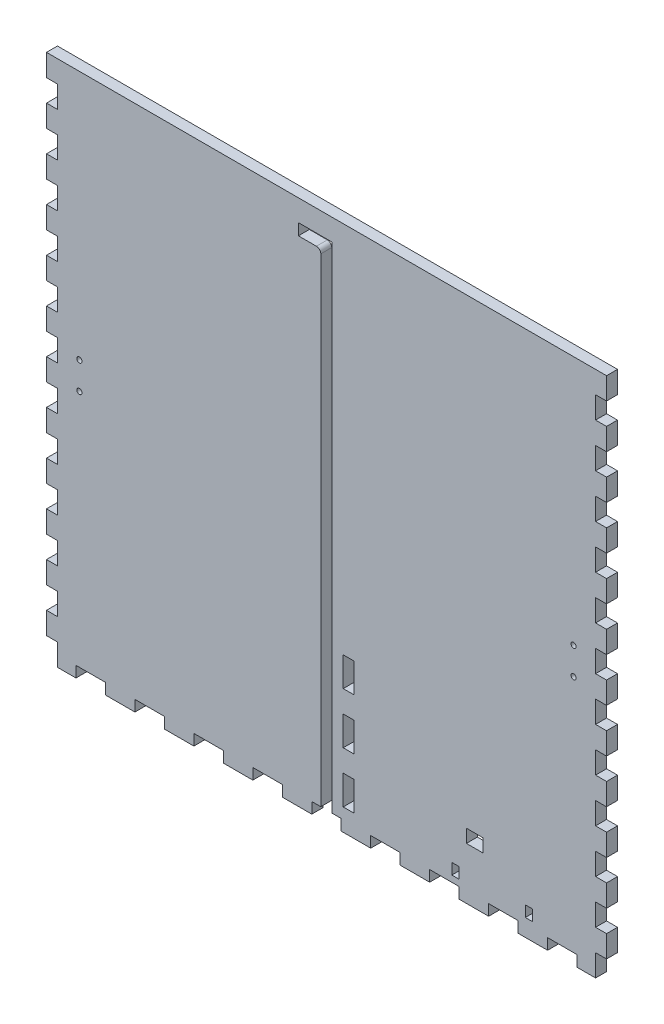
SolidWorks part; units mm, degrees
material "Acrylic (Medium-high impact)"
ref_plane "Front Plane" through (0, 0, 0) normal (0, 0, 1) x (1, 0, 0)
ref_plane "Top Plane" through (0, 0, 0) normal (0, 1, 0) x (1, 0, 0)
ref_plane "Right Plane" through (0, 0, 0) normal (1, 0, 0) x (0, 0, -1)
sketch "Sketch1" plane through (0, 0, 0) normal (0, 1, 0) x (1, 0, 0)
  line L1 (-161.925, 69.85) -> (161.925, 69.85)
  line L2 (-161.925, 69.85) -> (-161.925, -69.85)
  line L3 (-161.925, -69.85) -> (161.925, -69.85)
  line L4 (161.925, 69.85) -> (161.925, -69.85)
  point P4 (-161.925, 0)
  point P6 (0, 69.85)
  dimension "D1" = 139.7
  dimension "D2" = 323.85
extrude "Boss-Extrude1" add sketch "Sketch1" along normal blind 6.35
sketch "Sketch2" plane through (0, 6.35, 0) normal (0, 1, 0) x (1, 0, 0)
  line L0 (161.925, -69.85) -> (161.925, 69.85) construction
  line L1 (-161.925, 69.85) -> (161.925, 69.85)
  line L2 (-161.925, 69.85) -> (-161.925, -69.85)
  line L3 (-161.925, -69.85) -> (161.925, -69.85)
  line L4 (161.925, 69.85) -> (161.925, -69.85)
  line L5 (-161.925, -69.85) -> (161.925, -69.85) construction
  line L7 (-155.575, 63.5) -> (155.575, 63.5)
  line L8 (-155.575, 63.5) -> (-155.575, -63.5)
  line L9 (-155.575, -63.5) -> (155.575, -63.5)
  line L10 (155.575, 63.5) -> (155.575, -63.5)
  point P7 (-155.575, 0)
  point P14 (-161.925, 0)
  point P15 (0, -63.5)
  point P16 (0, -69.85)
  point P17 (155.575, 0)
  point P18 (161.925, 0)
  dimension "D1" = 6.35
  dimension "D2" = 6.35
extrude "Boss-Extrude2" add sketch "Sketch2" along normal blind 298.45
sketch "Sketch3" plane through (0, 0, 69.85) normal (0, 0, 1) x (1, 0, 0)
  line L0 (0, 304.8) -> (0, 0) construction
  line L2 (-155.575, 6.35) -> (155.575, 6.35) construction
  line L4 (-3.302, 283.21) -> (-3.302, 6.35)
  line L5 (-3.302, 6.35) -> (3.302, 6.35)
  line L6 (3.302, 292.354) -> (3.302, 6.35)
  line L7 (3.302, 292.354) -> (-16.256, 292.354)
  line L9 (-5.842, 285.75) -> (-16.256, 285.75)
  line L10 (-16.256, 292.354) -> (-16.256, 285.75)
  line L11 (3.302, 101.6) -> (16.002, 101.6) construction
  line L12 (-161.925, 0) -> (161.925, 0) construction
  line L13 (12.827, 88.9) -> (12.827, 101.6) construction
  line L14 (9.652, 88.9) -> (16.002, 88.9)
  line L15 (9.652, 88.9) -> (9.652, 71.9667)
  line L16 (9.652, 71.9667) -> (16.002, 71.9667)
  line L17 (16.002, 88.9) -> (16.002, 71.9667)
  line L18 (9.652, 42.3333) -> (16.002, 42.3333)
  line L19 (9.652, 42.3333) -> (9.652, 59.2667)
  line L20 (9.652, 59.2667) -> (16.002, 59.2667)
  line L21 (16.002, 42.3333) -> (16.002, 59.2667)
  line L26 (9.652, 29.6333) -> (16.002, 29.6333)
  line L27 (9.652, 29.6333) -> (9.652, 12.7)
  line L28 (9.652, 12.7) -> (16.002, 12.7)
  line L29 (16.002, 29.6333) -> (16.002, 12.7)
  line L30 (12.827, 59.2667) -> (12.827, 71.9667) construction
  line L31 (12.827, 29.6333) -> (12.827, 42.3333) construction
  line L32 (12.827, 12.7) -> (12.827, 0) construction
  line L33 (-161.925, 304.8) -> (161.925, 304.8) construction
  arc A0 (-3.302, 283.21) -> (-5.842, 285.75) centre (-5.842, 283.21) ccw
  point P5 (0, 6.35)
  point P44 (0, 0)
  dimension "D5" = 2.54
  dimension "D1" = 6.604
  dimension "D2" = 12.954
  dimension "D3" = 6.604
  dimension "D4" = 286.004
  dimension "D6" = 101.6
  dimension "D7" = 12.7
  dimension "D8" = 12.7
  dimension "D9" = 6.35
extrude "Door Slot" cut sketch "Sketch3" against normal blind 12.7
sketch "Sketch4" plane through (0, 0, -63.5) normal (0, 0, 1) x (1, 0, 0)
  line L0 (-161.925, 304.8) -> (161.925, 304.8) construction
  line L1 (-22.606, 304.8) -> (-16.256, 304.8)
  line L2 (-22.606, 304.8) -> (-22.606, 6.35)
  line L3 (-22.606, 6.35) -> (-16.256, 6.35)
  line L4 (-16.256, 304.8) -> (-16.256, 6.35)
  line L5 (6.477, 263.525) -> (6.477, 247.65) construction
  line L6 (-16.256, 292.354) -> (-16.256, 285.75) construction
  line L7 (3.302, 304.8) -> (9.652, 304.8)
  line L8 (3.302, 304.8) -> (3.302, 6.35)
  line L9 (3.302, 6.35) -> (9.652, 6.35)
  line L10 (9.652, 304.8) -> (9.652, 6.35)
  line L11 (155.575, 6.35) -> (-155.575, 6.35) construction
  line L12 (3.302, 6.35) -> (3.302, 292.354) construction
  line L13 (-16.256, 304.8) -> (-22.606, 304.8)
  line L14 (-16.256, 304.8) -> (-16.256, 292.1)
  line L15 (-16.256, 292.1) -> (-22.606, 292.1)
  line L16 (-22.606, 304.8) -> (-22.606, 292.1)
  line L17 (-16.256, 276.225) -> (-22.606, 276.225)
  line L18 (-16.256, 276.225) -> (-16.256, 263.525)
  line L19 (-16.256, 263.525) -> (-22.606, 263.525)
  line L20 (-22.606, 276.225) -> (-22.606, 263.525)
  line L21 (-22.606, 6.35) -> (-16.256, 6.35)
  line L22 (-22.606, 6.35) -> (-22.606, 19.05)
  line L23 (-22.606, 19.05) -> (-16.256, 19.05)
  line L24 (-16.256, 6.35) -> (-16.256, 19.05)
  line L25 (-22.606, 34.925) -> (-16.256, 34.925)
  line L26 (-22.606, 34.925) -> (-22.606, 47.625)
  line L27 (-22.606, 47.625) -> (-16.256, 47.625)
  line L28 (-16.256, 34.925) -> (-16.256, 47.625)
  line L29 (-22.606, 92.075) -> (-16.256, 92.075)
  line L30 (-22.606, 92.075) -> (-22.606, 104.775)
  line L31 (-22.606, 104.775) -> (-16.256, 104.775)
  line L32 (-16.256, 92.075) -> (-16.256, 104.775)
  line L33 (-22.606, 149.225) -> (-16.256, 149.225)
  line L34 (-22.606, 149.225) -> (-22.606, 161.925)
  line L35 (-22.606, 161.925) -> (-16.256, 161.925)
  line L36 (-16.256, 149.225) -> (-16.256, 161.925)
  line L37 (-22.606, 177.8) -> (-16.256, 177.8)
  line L38 (-22.606, 177.8) -> (-22.606, 190.5)
  line L39 (-22.606, 190.5) -> (-16.256, 190.5)
  line L40 (-16.256, 177.8) -> (-16.256, 190.5)
  line L41 (-22.606, 206.375) -> (-16.256, 206.375)
  line L42 (-22.606, 206.375) -> (-22.606, 219.075)
  line L43 (-22.606, 219.075) -> (-16.256, 219.075)
  line L44 (-16.256, 206.375) -> (-16.256, 219.075)
  line L45 (-22.606, 234.95) -> (-16.256, 234.95)
  line L46 (-22.606, 234.95) -> (-22.606, 247.65)
  line L47 (-22.606, 247.65) -> (-16.256, 247.65)
  line L48 (-16.256, 234.95) -> (-16.256, 247.65)
  line L49 (-16.256, 133.35) -> (-22.606, 133.35)
  line L50 (-16.256, 133.35) -> (-16.256, 120.65)
  line L51 (-16.256, 120.65) -> (-22.606, 120.65)
  line L52 (-22.606, 133.35) -> (-22.606, 120.65)
  line L53 (-16.256, 76.2) -> (-22.606, 76.2)
  line L54 (-16.256, 76.2) -> (-16.256, 63.5)
  line L55 (-16.256, 63.5) -> (-22.606, 63.5)
  line L56 (-22.606, 76.2) -> (-22.606, 63.5)
  line L57 (-19.431, 304.8) -> (-19.431, 292.1) construction
  line L58 (-19.431, 292.1) -> (-19.431, 276.225) construction
  line L59 (-19.431, 276.225) -> (-19.431, 263.525) construction
  line L60 (-19.431, 247.65) -> (-19.431, 234.95) construction
  line L61 (-19.431, 234.95) -> (-19.431, 219.075) construction
  line L62 (-19.431, 219.075) -> (-19.431, 206.375) construction
  line L63 (-19.431, 206.375) -> (-19.431, 190.5) construction
  line L64 (-19.431, 190.5) -> (-19.431, 177.8) construction
  line L65 (-19.431, 177.8) -> (-19.431, 161.925) construction
  line L66 (-19.431, 161.925) -> (-19.431, 149.225) construction
  line L67 (-19.431, 133.35) -> (-19.431, 120.65) construction
  line L68 (-19.431, 120.65) -> (-19.431, 104.775) construction
  line L69 (-19.431, 104.775) -> (-19.431, 92.075) construction
  line L70 (-19.431, 92.075) -> (-19.431, 76.2) construction
  line L71 (-19.431, 76.2) -> (-19.431, 63.5) construction
  line L72 (-19.431, 63.5) -> (-19.431, 47.625) construction
  line L73 (-19.431, 47.625) -> (-19.431, 34.925) construction
  line L74 (-19.431, 34.925) -> (-19.431, 19.05) construction
  line L75 (-19.431, 19.05) -> (-19.431, 6.35) construction
  line L76 (-19.431, 149.225) -> (-19.431, 133.35) construction
  line L77 (-19.431, 263.525) -> (-19.431, 247.65) construction
  line L78 (-6.477, 304.8) -> (-6.477, 0) construction
  line L79 (161.925, 304.8) -> (-161.925, 304.8) construction
  line L80 (161.925, 0) -> (-161.925, 0) construction
  line L81 (-6.477, 8.3493) -> (3.302, 8.3493) construction
  line L82 (-6.477, 8.3493) -> (-16.256, 8.3493) construction
  line L83 (6.477, 149.225) -> (6.477, 133.35) construction
  line L84 (6.477, 19.05) -> (6.477, 6.35) construction
  line L85 (6.477, 34.925) -> (6.477, 19.05) construction
  line L86 (6.477, 47.625) -> (6.477, 34.925) construction
  line L87 (6.477, 63.5) -> (6.477, 47.625) construction
  line L88 (6.477, 76.2) -> (6.477, 63.5) construction
  line L89 (6.477, 92.075) -> (6.477, 76.2) construction
  line L90 (6.477, 104.775) -> (6.477, 92.075) construction
  line L91 (6.477, 120.65) -> (6.477, 104.775) construction
  line L92 (6.477, 133.35) -> (6.477, 120.65) construction
  line L93 (6.477, 161.925) -> (6.477, 149.225) construction
  line L94 (6.477, 177.8) -> (6.477, 161.925) construction
  line L95 (6.477, 190.5) -> (6.477, 177.8) construction
  line L96 (6.477, 206.375) -> (6.477, 190.5) construction
  line L97 (6.477, 219.075) -> (6.477, 206.375) construction
  line L98 (6.477, 234.95) -> (6.477, 219.075) construction
  line L99 (6.477, 247.65) -> (6.477, 234.95) construction
  line L100 (6.477, 276.225) -> (6.477, 263.525) construction
  line L101 (6.477, 292.1) -> (6.477, 276.225) construction
  line L102 (6.477, 304.8) -> (6.477, 292.1) construction
  line L103 (9.652, 76.2) -> (9.652, 63.5)
  line L104 (3.302, 63.5) -> (9.652, 63.5)
  line L105 (3.302, 76.2) -> (3.302, 63.5)
  line L106 (3.302, 76.2) -> (9.652, 76.2)
  line L107 (9.652, 133.35) -> (9.652, 120.65)
  line L108 (3.302, 120.65) -> (9.652, 120.65)
  line L109 (3.302, 133.35) -> (3.302, 120.65)
  line L110 (3.302, 133.35) -> (9.652, 133.35)
  line L111 (3.302, 234.95) -> (3.302, 247.65)
  line L112 (9.652, 247.65) -> (3.302, 247.65)
  line L113 (9.652, 234.95) -> (9.652, 247.65)
  line L114 (9.652, 234.95) -> (3.302, 234.95)
  line L115 (3.302, 206.375) -> (3.302, 219.075)
  line L116 (9.652, 219.075) -> (3.302, 219.075)
  line L117 (9.652, 206.375) -> (9.652, 219.075)
  line L118 (9.652, 206.375) -> (3.302, 206.375)
  line L119 (3.302, 177.8) -> (3.302, 190.5)
  line L120 (9.652, 190.5) -> (3.302, 190.5)
  line L121 (9.652, 177.8) -> (9.652, 190.5)
  line L122 (9.652, 177.8) -> (3.302, 177.8)
  line L123 (3.302, 149.225) -> (3.302, 161.925)
  line L124 (9.652, 161.925) -> (3.302, 161.925)
  line L125 (9.652, 149.225) -> (9.652, 161.925)
  line L126 (9.652, 149.225) -> (3.302, 149.225)
  line L127 (3.302, 92.075) -> (3.302, 104.775)
  line L128 (9.652, 104.775) -> (3.302, 104.775)
  line L129 (9.652, 92.075) -> (9.652, 104.775)
  line L130 (9.652, 92.075) -> (3.302, 92.075)
  line L131 (3.302, 34.925) -> (3.302, 47.625)
  line L132 (9.652, 47.625) -> (3.302, 47.625)
  line L133 (9.652, 34.925) -> (9.652, 47.625)
  line L134 (9.652, 34.925) -> (3.302, 34.925)
  line L135 (3.302, 6.35) -> (3.302, 19.05)
  line L136 (9.652, 19.05) -> (3.302, 19.05)
  line L137 (9.652, 6.35) -> (9.652, 19.05)
  line L138 (9.652, 6.35) -> (3.302, 6.35)
  line L139 (9.652, 276.225) -> (9.652, 263.525)
  line L140 (3.302, 263.525) -> (9.652, 263.525)
  line L141 (3.302, 276.225) -> (3.302, 263.525)
  line L142 (3.302, 276.225) -> (9.652, 276.225)
  line L143 (9.652, 304.8) -> (9.652, 292.1)
  line L144 (3.302, 292.1) -> (9.652, 292.1)
  line L145 (3.302, 304.8) -> (3.302, 292.1)
  line L146 (3.302, 304.8) -> (9.652, 304.8)
  line L147 (3.302, 304.8) -> (3.302, 6.35)
  line L148 (9.652, 6.35) -> (3.302, 6.35)
  line L149 (9.652, 304.8) -> (9.652, 6.35)
  line L150 (9.652, 304.8) -> (3.302, 304.8)
  point P14 (-16.256, 289.052)
  dimension "D1" = 6.35
  dimension "D2" = 12.7
extrude "Door Guide Holes" cut sketch "Sketch4" against normal up to next contours L17 L4 L15 L2 | L2 L47 L4 L19 | L45 L2 L43 L4 | L41 L2 L39 L4 | L37 L2 L35 L4 | L49 L4 L33 L2 | L4 L51 L2 L31 | L53 L4 L29 L2 | L4 L55 L2 L27 | L25 L2 L23 L4 region at (-19.431, 284.1625, -63.5) region at (-19.431, 255.5875, -63.5) region at (-19.431, 227.0125, -63.5) region at (-19.431, 198.4375, -63.5) region at (-19.431, 169.8625, -63.5) region at (-19.431, 141.2875, -63.5) region at (-19.431, 112.7125, -63.5) region at (-19.431, 84.1375, -63.5) region at (-19.431, 55.5625, -63.5) region at (-19.431, 26.9875, -63.5)
ref_plane "Plane1" through (-6.477, 0, 0) normal (-1, 0, 0) x (0, 0, 1)
mirror "Mirror1" about plane through (-6.477, 0, 0) normal (-1, 0, 0) of "Door Guide Holes"
sketch "Lever Holes" plane through (0, 0, 69.85) normal (0, 0, 1) x (1, 0, 0)
  line L0 (80.899, 37.685) -> (90.551, 37.685)
  line L1 (80.899, 37.685) -> (80.899, 30.065)
  line L2 (80.899, 30.065) -> (90.551, 30.065)
  line L3 (90.551, 37.685) -> (90.551, 30.065)
  line L4 (72.475, 16.35) -> (76.475, 16.35)
  line L5 (72.475, 16.35) -> (72.475, 10)
  line L6 (72.475, 10) -> (76.475, 10)
  line L7 (76.475, 16.35) -> (76.475, 10)
  line L8 (114.975, 16.35) -> (118.975, 16.35)
  line L9 (114.975, 16.35) -> (114.975, 10)
  line L10 (114.975, 10) -> (118.975, 10)
  line L11 (118.975, 16.35) -> (118.975, 10)
  line L12 (76.475, 13.175) -> (114.975, 13.175) construction
  line L14 (3.302, 6.35) -> (155.575, 6.35) construction
  line L15 (155.575, 6.35) -> (-155.575, 6.35) construction
  line L16 (142.875, 160.275) -> (142.875, 144.525) construction
  line L17 (161.925, 304.8) -> (161.925, 0) construction
  line L18 (0, -76.835) -> (0, 76.835) construction
  circle A0 centre (142.875, 160.275) radius 1.5
  circle A1 centre (142.875, 144.525) radius 1.5
  circle A2 centre (-142.875, 160.275) radius 1.5
  circle A3 centre (-142.875, 144.525) radius 1.5
  point P13 (85.725, 30.065)
  point P31 (142.875, 152.4)
  point P32 (161.925, 152.4)
  dimension "D10" = 3
  dimension "D1" = 9.652
  dimension "D2" = 7.62
  dimension "D3" = 4
  dimension "D4" = 6.35
  dimension "D5" = 38.5
  dimension "D6" = 31.335
  dimension "D7" = 10
  dimension "D8" = 76.2
  dimension "D9" = 13.25
  dimension "D11" = 15.75
  dimension "D12" = 19.05
extrude "LeverHole Cut" cut sketch "Lever Holes" against normal through all
sketch "Sketch7" plane through (161.925, 0, 0) normal (1, 0, 0) x (0, 0, -1)
  line L0 (-37.211, 92.583) -> (37.211, 92.583)
  line L1 (-37.211, 92.583) -> (-37.211, 18.161)
  line L2 (-37.211, 18.161) -> (37.211, 18.161)
  line L3 (37.211, 92.583) -> (37.211, 18.161)
  line L4 (-69.85, 0) -> (69.85, 0) construction
  circle A0 centre (0, 55.372) radius 26.9875
  circle A1 centre (-37.211, 92.583) radius 3.175
  circle A2 centre (37.211, 92.583) radius 3.175
  circle A3 centre (-37.211, 18.161) radius 3.175
  circle A4 centre (37.211, 18.161) radius 3.175
  point P9 (0, 18.161)
  point P10 (-37.211, 55.372)
  dimension "D3" = 53.975
  dimension "D4" = 6.35
  dimension "D1" = 74.422
  dimension "D2" = 55.372
extrude "Cut-Extrude2" cut sketch "Sketch7" against normal up to next contours A0 | L0 A1 L1 | L1 A1 L0 | L3 A2 L0 | L0 A2 L3 | L2 A3 L1 | L1 A3 L2 | L2 A4 L3 | L3 A4 L2 region at (161.925, 93.0322, 37.6602) region at (161.925, 91.2355, 35.8635) region at (161.925, 93.0322, -37.6602) region at (161.925, 91.2355, -35.8635) region at (161.925, 19.5085, 35.8635) region at (161.925, 17.7118, 37.6602) region at (161.925, 17.7118, -37.6602) region at (161.925, 19.5085, -35.8635) region at (161.925, 55.372, 0)
sketch "Sketch8" plane through (-161.925, 0, 0) normal (-1, 0, 0) x (0, 0, 1)
  line L0 (-69.85, 0) -> (69.85, 0) construction
  circle A0 centre (0, 19.05) radius 3.175
  point P6 (0, 0)
  dimension "D1" = 6.35
  dimension "D2" = 19.05
extrude "Cut-Extrude3" cut sketch "Sketch8" against normal up to next
sketch "Bottom" plane through (0, 0, 0) normal (0, -1, 0) x (1, 0, 0)
  line L0 (-155.575, 63.5) -> (155.575, 63.5) construction
  line L1 (-161.925, 69.85) -> (-144.8803, 69.85)
  line L2 (-161.925, 69.85) -> (-161.925, 63.5)
  line L3 (-161.925, 63.5) -> (-144.8803, 63.5)
  line L4 (-144.8803, 69.85) -> (-144.8803, 63.5)
  line L5 (-144.8803, 69.85) -> (-127.8355, 69.85)
  line L6 (-144.8803, 69.85) -> (-144.8803, 63.5)
  line L7 (-144.8803, 63.5) -> (-127.8355, 63.5)
  line L8 (-127.8355, 69.85) -> (-127.8355, 63.5)
  line L9 (-127.8355, 69.85) -> (-110.7908, 69.85)
  line L10 (-127.8355, 69.85) -> (-127.8355, 63.5)
  line L11 (-127.8355, 63.5) -> (-110.7908, 63.5)
  line L12 (-110.7908, 69.85) -> (-110.7908, 63.5)
  line L13 (-110.7908, 69.85) -> (-93.7461, 69.85)
  line L14 (-110.7908, 69.85) -> (-110.7908, 63.5)
  line L15 (-110.7908, 63.5) -> (-93.7461, 63.5)
  line L16 (-93.7461, 69.85) -> (-93.7461, 63.5)
  line L17 (-161.925, 69.85) -> (161.925, 69.85) construction
  line L18 (-16.256, 63.5) -> (3.302, 63.5) construction
  line L19 (-93.7461, 69.85) -> (-76.7013, 69.85)
  line L20 (-93.7461, 69.85) -> (-93.7461, 63.5)
  line L21 (-93.7461, 63.5) -> (-76.7013, 63.5)
  line L22 (-76.7013, 69.85) -> (-76.7013, 63.5)
  line L23 (-76.7013, 69.85) -> (-59.6566, 69.85)
  line L24 (-76.7013, 69.85) -> (-76.7013, 63.5)
  line L25 (-76.7013, 63.5) -> (-59.6566, 63.5)
  line L26 (-59.6566, 69.85) -> (-59.6566, 63.5)
  line L27 (-59.6566, 69.85) -> (-42.6118, 69.85)
  line L28 (-59.6566, 69.85) -> (-59.6566, 63.5)
  line L29 (-59.6566, 63.5) -> (-42.6118, 63.5)
  line L30 (-42.6118, 69.85) -> (-42.6118, 63.5)
  line L31 (-42.6118, 69.85) -> (-25.5671, 69.85)
  line L32 (-42.6118, 69.85) -> (-42.6118, 63.5)
  line L33 (-42.6118, 63.5) -> (-25.5671, 63.5)
  line L34 (-25.5671, 69.85) -> (-25.5671, 63.5)
  line L36 (-25.5671, 69.85) -> (-8.5224, 69.85)
  line L37 (-25.5671, 69.85) -> (-25.5671, 63.5)
  line L38 (-25.5671, 63.5) -> (-8.5224, 63.5)
  line L39 (-8.5224, 69.85) -> (-8.5224, 63.5)
  line L40 (-8.5224, 69.85) -> (8.5224, 69.85)
  line L41 (-8.5224, 69.85) -> (-8.5224, 63.5)
  line L42 (-8.5224, 63.5) -> (8.5224, 63.5)
  line L43 (8.5224, 69.85) -> (8.5224, 63.5)
  line L44 (8.5224, 69.85) -> (25.5671, 69.85)
  line L45 (8.5224, 69.85) -> (8.5224, 63.5)
  line L46 (8.5224, 63.5) -> (25.5671, 63.5)
  line L47 (25.5671, 69.85) -> (25.5671, 63.5)
  line L48 (25.5671, 69.85) -> (42.6118, 69.85)
  line L49 (25.5671, 69.85) -> (25.5671, 63.5)
  line L50 (25.5671, 63.5) -> (42.6118, 63.5)
  line L51 (42.6118, 69.85) -> (42.6118, 63.5)
  line L52 (42.6118, 69.85) -> (59.6566, 69.85)
  line L53 (42.6118, 69.85) -> (42.6118, 63.5)
  line L54 (42.6118, 63.5) -> (59.6566, 63.5)
  line L55 (59.6566, 69.85) -> (59.6566, 63.5)
  line L56 (59.6566, 69.85) -> (76.7013, 69.85)
  line L57 (59.6566, 69.85) -> (59.6566, 63.5)
  line L58 (59.6566, 63.5) -> (76.7013, 63.5)
  line L59 (76.7013, 69.85) -> (76.7013, 63.5)
  line L60 (76.7013, 69.85) -> (93.7461, 69.85)
  line L61 (76.7013, 69.85) -> (76.7013, 63.5)
  line L62 (76.7013, 63.5) -> (93.7461, 63.5)
  line L63 (93.7461, 69.85) -> (93.7461, 63.5)
  line L64 (93.7461, 69.85) -> (110.7908, 69.85)
  line L65 (93.7461, 69.85) -> (93.7461, 63.5)
  line L66 (93.7461, 63.5) -> (110.7908, 63.5)
  line L67 (110.7908, 69.85) -> (110.7908, 63.5)
  line L68 (110.7908, 69.85) -> (127.8355, 69.85)
  line L69 (110.7908, 69.85) -> (110.7908, 63.5)
  line L70 (110.7908, 63.5) -> (127.8355, 63.5)
  line L71 (127.8355, 69.85) -> (127.8355, 63.5)
  line L72 (127.8355, 69.85) -> (144.8803, 69.85)
  line L73 (127.8355, 69.85) -> (127.8355, 63.5)
  line L74 (127.8355, 63.5) -> (144.8803, 63.5)
  line L75 (144.8803, 69.85) -> (144.8803, 63.5)
  line L76 (-155.575, -63.5) -> (-155.575, 63.5) construction
  line L77 (-161.925, 69.85) -> (-155.575, 69.85)
  line L78 (-161.925, 69.85) -> (-161.925, 57.15)
  line L79 (-161.925, 57.15) -> (-155.575, 57.15)
  line L80 (-155.575, 69.85) -> (-155.575, 57.15)
  line L82 (-161.925, 57.15) -> (-155.575, 57.15)
  line L83 (-161.925, 57.15) -> (-161.925, 44.45)
  line L84 (-161.925, 44.45) -> (-155.575, 44.45)
  line L85 (-155.575, 57.15) -> (-155.575, 44.45)
  line L86 (-161.925, 44.45) -> (-155.575, 44.45)
  line L87 (-161.925, 44.45) -> (-161.925, 31.75)
  line L88 (-161.925, 31.75) -> (-155.575, 31.75)
  line L89 (-155.575, 44.45) -> (-155.575, 31.75)
  line L90 (-161.925, 31.75) -> (-155.575, 31.75)
  line L91 (-161.925, 31.75) -> (-161.925, 19.05)
  line L92 (-161.925, 19.05) -> (-155.575, 19.05)
  line L93 (-155.575, 31.75) -> (-155.575, 19.05)
  line L94 (-161.925, 19.05) -> (-155.575, 19.05)
  line L95 (-161.925, 19.05) -> (-161.925, 6.35)
  line L96 (-161.925, 6.35) -> (-155.575, 6.35)
  line L97 (-155.575, 19.05) -> (-155.575, 6.35)
  line L98 (-161.925, 6.35) -> (-155.575, 6.35)
  line L99 (-161.925, 6.35) -> (-161.925, -6.35)
  line L100 (-161.925, -6.35) -> (-155.575, -6.35)
  line L101 (-155.575, 6.35) -> (-155.575, -6.35)
  line L102 (-161.925, -6.35) -> (-155.575, -6.35)
  line L103 (-161.925, -6.35) -> (-161.925, -19.05)
  line L104 (-161.925, -19.05) -> (-155.575, -19.05)
  line L105 (-155.575, -6.35) -> (-155.575, -19.05)
  line L106 (-161.925, -19.05) -> (-155.575, -19.05)
  line L107 (-161.925, -19.05) -> (-161.925, -31.75)
  line L108 (-161.925, -31.75) -> (-155.575, -31.75)
  line L109 (-155.575, -19.05) -> (-155.575, -31.75)
  line L110 (-161.925, -31.75) -> (-155.575, -31.75)
  line L111 (-161.925, -31.75) -> (-161.925, -44.45)
  line L112 (-161.925, -44.45) -> (-155.575, -44.45)
  line L113 (-155.575, -31.75) -> (-155.575, -44.45)
  line L114 (-161.925, -44.45) -> (-155.575, -44.45)
  line L115 (-161.925, -44.45) -> (-161.925, -57.15)
  line L116 (-161.925, -57.15) -> (-155.575, -57.15)
  line L117 (-155.575, -44.45) -> (-155.575, -57.15)
  line L118 (161.925, 69.85) -> (161.925, -69.85) construction
  line L119 (144.8803, 69.85) -> (161.925, 69.85)
  line L120 (144.8803, 69.85) -> (144.8803, 63.5)
  line L121 (144.8803, 63.5) -> (161.925, 63.5)
  line L122 (161.925, 69.85) -> (161.925, 63.5)
  line L123 (161.925, -69.85) -> (-161.925, -69.85) construction
  line L124 (-161.925, -57.15) -> (-155.575, -57.15)
  line L125 (-161.925, -57.15) -> (-161.925, -69.85)
  line L126 (-161.925, -69.85) -> (-155.575, -69.85)
  line L127 (-155.575, -57.15) -> (-155.575, -69.85)
  line L128 (167.64, 0) -> (-167.64, 0) construction
  line L129 (161.925, -69.85) -> (161.925, -63.5)
  line L130 (144.8803, -63.5) -> (161.925, -63.5)
  line L131 (144.8803, -69.85) -> (161.925, -69.85)
  line L132 (144.8803, -69.85) -> (144.8803, -63.5)
  line L133 (127.8355, -63.5) -> (144.8803, -63.5)
  line L134 (127.8355, -69.85) -> (144.8803, -69.85)
  line L135 (127.8355, -69.85) -> (127.8355, -63.5)
  line L136 (110.7908, -63.5) -> (127.8355, -63.5)
  line L137 (110.7908, -69.85) -> (127.8355, -69.85)
  line L138 (110.7908, -69.85) -> (110.7908, -63.5)
  line L139 (93.7461, -63.5) -> (110.7908, -63.5)
  line L140 (93.7461, -69.85) -> (110.7908, -69.85)
  line L141 (93.7461, -69.85) -> (93.7461, -63.5)
  line L142 (76.7013, -63.5) -> (93.7461, -63.5)
  line L143 (76.7013, -69.85) -> (93.7461, -69.85)
  line L144 (59.6566, -63.5) -> (76.7013, -63.5)
  line L145 (76.7013, -69.85) -> (76.7013, -63.5)
  line L146 (59.6566, -69.85) -> (76.7013, -69.85)
  line L147 (59.6566, -69.85) -> (59.6566, -63.5)
  line L148 (42.6118, -63.5) -> (59.6566, -63.5)
  line L149 (42.6118, -69.85) -> (59.6566, -69.85)
  line L150 (42.6118, -69.85) -> (42.6118, -63.5)
  line L151 (25.5671, -63.5) -> (42.6118, -63.5)
  line L152 (25.5671, -69.85) -> (42.6118, -69.85)
  line L153 (25.5671, -69.85) -> (25.5671, -63.5)
  line L154 (8.5224, -69.85) -> (25.5671, -69.85)
  line L155 (8.5224, -63.5) -> (25.5671, -63.5)
  line L156 (8.5224, -69.85) -> (8.5224, -63.5)
  line L157 (-8.5224, -63.5) -> (8.5224, -63.5)
  line L158 (-8.5224, -69.85) -> (8.5224, -69.85)
  line L159 (-25.5671, -63.5) -> (-8.5224, -63.5)
  line L160 (-8.5224, -69.85) -> (-8.5224, -63.5)
  line L161 (-25.5671, -69.85) -> (-8.5224, -69.85)
  line L162 (-25.5671, -69.85) -> (-25.5671, -63.5)
  line L163 (-42.6118, -63.5) -> (-25.5671, -63.5)
  line L164 (-42.6118, -69.85) -> (-25.5671, -69.85)
  line L165 (-42.6118, -69.85) -> (-42.6118, -63.5)
  line L166 (-59.6566, -63.5) -> (-42.6118, -63.5)
  line L167 (-59.6566, -69.85) -> (-42.6118, -69.85)
  line L168 (-59.6566, -69.85) -> (-59.6566, -63.5)
  line L169 (-76.7013, -69.85) -> (-59.6566, -69.85)
  line L170 (-76.7013, -63.5) -> (-59.6566, -63.5)
  line L171 (-93.7461, -63.5) -> (-76.7013, -63.5)
  line L172 (-76.7013, -69.85) -> (-76.7013, -63.5)
  line L173 (-93.7461, -69.85) -> (-76.7013, -69.85)
  line L174 (-110.7908, -69.85) -> (-93.7461, -69.85)
  line L175 (-110.7908, -63.5) -> (-93.7461, -63.5)
  line L176 (-93.7461, -69.85) -> (-93.7461, -63.5)
  line L177 (-127.8355, -69.85) -> (-127.8355, -63.5)
  line L178 (-127.8355, -69.85) -> (-110.7908, -69.85)
  line L179 (-110.7908, -69.85) -> (-110.7908, -63.5)
  line L180 (-127.8355, -63.5) -> (-110.7908, -63.5)
  line L181 (-144.8803, -63.5) -> (-127.8355, -63.5)
  line L182 (-144.8803, -69.85) -> (-127.8355, -69.85)
  line L183 (-144.8803, -69.85) -> (-144.8803, -63.5)
  line L184 (-161.925, -69.85) -> (-144.8803, -69.85)
  line L185 (-161.925, -69.85) -> (-161.925, -63.5)
  line L186 (-161.925, -63.5) -> (-144.8803, -63.5)
  line L187 (0, -76.835) -> (0, 76.835) construction
  line L188 (161.925, -69.85) -> (155.575, -69.85)
  line L189 (155.575, -57.15) -> (155.575, -69.85)
  line L190 (161.925, -57.15) -> (161.925, -69.85)
  line L191 (161.925, -57.15) -> (155.575, -57.15)
  line L192 (155.575, -44.45) -> (155.575, -57.15)
  line L193 (161.925, -44.45) -> (161.925, -57.15)
  line L194 (161.925, -44.45) -> (155.575, -44.45)
  line L195 (155.575, -31.75) -> (155.575, -44.45)
  line L196 (161.925, -31.75) -> (161.925, -44.45)
  line L197 (161.925, -31.75) -> (155.575, -31.75)
  line L198 (161.925, -19.05) -> (161.925, -31.75)
  line L199 (155.575, -19.05) -> (155.575, -31.75)
  line L200 (155.575, -6.35) -> (155.575, -19.05)
  line L201 (161.925, -6.35) -> (161.925, -19.05)
  line L202 (161.925, -19.05) -> (155.575, -19.05)
  line L203 (161.925, -6.35) -> (155.575, -6.35)
  line L204 (155.575, 6.35) -> (155.575, -6.35)
  line L205 (161.925, 6.35) -> (161.925, -6.35)
  line L206 (161.925, 6.35) -> (155.575, 6.35)
  line L207 (155.575, 19.05) -> (155.575, 6.35)
  line L208 (161.925, 19.05) -> (161.925, 6.35)
  line L209 (161.925, 19.05) -> (155.575, 19.05)
  line L210 (161.925, 31.75) -> (155.575, 31.75)
  line L211 (161.925, 44.45) -> (155.575, 44.45)
  line L212 (161.925, 57.15) -> (155.575, 57.15)
  line L213 (155.575, 31.75) -> (155.575, 19.05)
  line L214 (161.925, 31.75) -> (161.925, 19.05)
  line L215 (155.575, 44.45) -> (155.575, 31.75)
  line L216 (161.925, 44.45) -> (161.925, 31.75)
  line L217 (155.575, 57.15) -> (155.575, 44.45)
  line L218 (161.925, 57.15) -> (161.925, 44.45)
  line L219 (155.575, 69.85) -> (155.575, 57.15)
  line L220 (161.925, 69.85) -> (161.925, 57.15)
sketch "Front/Back" plane through (0, 0, 69.85) normal (0, 0, 1) x (1, 0, 0)
  line L0 (-155.575, 6.35) -> (-3.302, 6.35) construction
  line L1 (-161.925, 0) -> (-144.8803, 0)
  line L2 (-161.925, 0) -> (-161.925, 6.35)
  line L3 (-161.925, 6.35) -> (-144.8803, 6.35)
  line L4 (-144.8803, 0) -> (-144.8803, 6.35)
  line L5 (-161.925, 0) -> (161.925, 0) construction
  line L6 (-127.8355, 0) -> (-110.7908, 0) construction
  line L7 (-144.8803, 6.35) -> (-127.8355, 6.35)
  line L8 (-144.8803, 6.35) -> (-144.8803, 0)
  line L9 (-144.8803, 0) -> (-127.8355, 0)
  line L10 (-127.8355, 6.35) -> (-127.8355, 0)
  line L11 (-93.7461, 0) -> (-76.7013, 0) construction
  line L12 (-127.8355, 6.35) -> (-110.7908, 6.35)
  line L13 (-127.8355, 6.35) -> (-127.8355, 0)
  line L14 (-127.8355, 0) -> (-110.7908, 0)
  line L15 (-110.7908, 6.35) -> (-110.7908, 0)
  line L16 (-110.7908, 6.35) -> (-93.7461, 6.35)
  line L17 (-110.7908, 6.35) -> (-110.7908, 0)
  line L18 (-110.7908, 0) -> (-93.7461, 0)
  line L19 (-93.7461, 6.35) -> (-93.7461, 0)
  line L20 (-76.7013, 0) -> (-59.6566, 0) construction
  line L21 (-93.7461, 6.35) -> (-76.7013, 6.35)
  line L22 (-93.7461, 6.35) -> (-93.7461, 0)
  line L23 (-93.7461, 0) -> (-76.7013, 0)
  line L24 (-76.7013, 6.35) -> (-76.7013, 0)
  line L25 (-76.7013, 6.35) -> (-59.6566, 6.35)
  line L26 (-76.7013, 6.35) -> (-76.7013, 0)
  line L27 (-76.7013, 0) -> (-59.6566, 0)
  line L28 (-59.6566, 6.35) -> (-59.6566, 0)
  line L29 (-59.6566, 0) -> (-42.6118, 0) construction
  line L30 (-59.6566, 6.35) -> (-42.6118, 6.35)
  line L31 (-59.6566, 6.35) -> (-59.6566, 0)
  line L32 (-59.6566, 0) -> (-42.6118, 0)
  line L33 (-42.6118, 6.35) -> (-42.6118, 0)
  line L34 (-25.5671, 0) -> (-8.5224, 0) construction
  line L35 (-42.6118, 6.35) -> (-25.5671, 6.35)
  line L36 (-42.6118, 6.35) -> (-42.6118, 0)
  line L37 (-42.6118, 0) -> (-25.5671, 0)
  line L38 (-25.5671, 6.35) -> (-25.5671, 0)
  line L39 (8.5224, 0) -> (25.5671, 0) construction
  line L40 (-25.5671, 6.35) -> (-8.5224, 6.35)
  line L41 (-25.5671, 6.35) -> (-25.5671, 0)
  line L42 (-25.5671, 0) -> (-8.5224, 0)
  line L43 (-8.5224, 6.35) -> (-8.5224, 0)
  line L44 (-8.5224, 6.35) -> (8.5224, 6.35)
  line L45 (-8.5224, 6.35) -> (-8.5224, 0)
  line L46 (-8.5224, 0) -> (8.5224, 0)
  line L47 (8.5224, 6.35) -> (8.5224, 0)
  line L48 (8.5224, 0) -> (25.5671, 0) construction
  line L49 (42.6118, 0) -> (59.6566, 0) construction
  line L50 (8.5224, 6.35) -> (25.5671, 6.35)
  line L51 (8.5224, 6.35) -> (8.5224, 0)
  line L52 (8.5224, 0) -> (25.5671, 0)
  line L53 (25.5671, 6.35) -> (25.5671, 0)
  line L54 (25.5671, 6.35) -> (42.6118, 6.35)
  line L55 (25.5671, 6.35) -> (25.5671, 0)
  line L56 (25.5671, 0) -> (42.6118, 0)
  line L57 (42.6118, 6.35) -> (42.6118, 0)
  line L58 (76.7013, 0) -> (93.7461, 0) construction
  line L59 (42.6118, 6.35) -> (59.6566, 6.35)
  line L60 (42.6118, 6.35) -> (42.6118, 0)
  line L61 (42.6118, 0) -> (59.6566, 0)
  line L62 (59.6566, 6.35) -> (59.6566, 0)
  line L63 (59.6566, 6.35) -> (76.7013, 6.35)
  line L64 (59.6566, 6.35) -> (59.6566, 0)
  line L65 (59.6566, 0) -> (76.7013, 0)
  line L66 (76.7013, 6.35) -> (76.7013, 0)
  line L67 (59.6566, 0) -> (76.7013, 0) construction
  line L68 (110.7908, 0) -> (127.8355, 0) construction
  line L69 (76.7013, 6.35) -> (93.7461, 6.35)
  line L70 (76.7013, 6.35) -> (76.7013, 0)
  line L71 (76.7013, 0) -> (93.7461, 0)
  line L72 (93.7461, 6.35) -> (93.7461, 0)
  line L73 (93.7461, 6.35) -> (110.7908, 6.35)
  line L74 (93.7461, 6.35) -> (93.7461, 0)
  line L75 (93.7461, 0) -> (110.7908, 0)
  line L76 (110.7908, 6.35) -> (110.7908, 0)
  line L77 (127.8355, 0) -> (144.8803, 0) construction
  line L78 (110.7908, 6.35) -> (127.8355, 6.35)
  line L79 (110.7908, 6.35) -> (110.7908, 0)
  line L80 (110.7908, 0) -> (127.8355, 0)
  line L81 (127.8355, 6.35) -> (127.8355, 0)
  line L82 (127.8355, 0) -> (144.8803, 0) construction
  line L84 (127.8355, 6.35) -> (144.8803, 6.35)
  line L85 (127.8355, 6.35) -> (127.8355, 0)
  line L86 (127.8355, 0) -> (144.8803, 0)
  line L87 (144.8803, 6.35) -> (144.8803, 0)
  line L88 (144.8803, 6.35) -> (161.925, 6.35)
  line L89 (144.8803, 6.35) -> (144.8803, 0)
  line L90 (144.8803, 0) -> (161.925, 0)
  line L91 (161.925, 6.35) -> (161.925, 0)
  line L92 (-155.575, 304.8) -> (-155.575, 6.35) construction
  line L93 (-161.925, 0) -> (-155.575, 0)
  line L94 (-161.925, 0) -> (-161.925, 12.7)
  line L95 (-161.925, 12.7) -> (-155.575, 12.7)
  line L96 (-155.575, 0) -> (-155.575, 12.7)
  line L97 (-161.925, 304.8) -> (-161.925, 0) construction
  line L98 (-161.925, 12.7) -> (-155.575, 12.7)
  line L99 (-161.925, 12.7) -> (-161.925, 25.4)
  line L100 (-161.925, 25.4) -> (-155.575, 25.4)
  line L101 (-155.575, 12.7) -> (-155.575, 25.4)
  line L102 (-161.925, 25.4) -> (-155.575, 25.4)
  line L103 (-161.925, 25.4) -> (-161.925, 38.1)
  line L104 (-161.925, 38.1) -> (-155.575, 38.1)
  line L105 (-155.575, 25.4) -> (-155.575, 38.1)
  line L106 (-161.925, 38.1) -> (-155.575, 38.1)
  line L107 (-161.925, 38.1) -> (-161.925, 50.8)
  line L108 (-161.925, 50.8) -> (-155.575, 50.8)
  line L109 (-155.575, 38.1) -> (-155.575, 50.8)
  line L110 (-161.925, 50.8) -> (-155.575, 50.8)
  line L111 (-161.925, 50.8) -> (-161.925, 63.5)
  line L112 (-161.925, 63.5) -> (-155.575, 63.5)
  line L113 (-155.575, 50.8) -> (-155.575, 63.5)
  line L114 (-161.925, 63.5) -> (-155.575, 63.5)
  line L115 (-161.925, 63.5) -> (-161.925, 76.2)
  line L116 (-161.925, 76.2) -> (-155.575, 76.2)
  line L117 (-155.575, 63.5) -> (-155.575, 76.2)
  line L118 (-161.925, 76.2) -> (-155.575, 76.2)
  line L119 (-161.925, 76.2) -> (-161.925, 88.9)
  line L120 (-161.925, 88.9) -> (-155.575, 88.9)
  line L121 (-155.575, 76.2) -> (-155.575, 88.9)
  line L122 (-161.925, 88.9) -> (-155.575, 88.9)
  line L123 (-161.925, 88.9) -> (-161.925, 101.6)
  line L124 (-161.925, 101.6) -> (-155.575, 101.6)
  line L125 (-155.575, 88.9) -> (-155.575, 101.6)
  line L126 (-161.925, 101.6) -> (-155.575, 101.6)
  line L127 (-161.925, 101.6) -> (-161.925, 114.3)
  line L128 (-161.925, 114.3) -> (-155.575, 114.3)
  line L129 (-155.575, 101.6) -> (-155.575, 114.3)
  line L130 (-161.925, 114.3) -> (-155.575, 114.3)
  line L131 (-161.925, 114.3) -> (-161.925, 127)
  line L132 (-161.925, 127) -> (-155.575, 127)
  line L133 (-155.575, 114.3) -> (-155.575, 127)
  line L134 (-161.925, 127) -> (-155.575, 127)
  line L135 (-161.925, 127) -> (-161.925, 139.7)
  line L136 (-161.925, 139.7) -> (-155.575, 139.7)
  line L137 (-155.575, 127) -> (-155.575, 139.7)
  line L138 (-161.925, 139.7) -> (-155.575, 139.7)
  line L139 (-161.925, 139.7) -> (-161.925, 152.4)
  line L140 (-161.925, 152.4) -> (-155.575, 152.4)
  line L141 (-155.575, 139.7) -> (-155.575, 152.4)
  line L142 (-161.925, 152.4) -> (-155.575, 152.4)
  line L143 (-161.925, 152.4) -> (-161.925, 165.1)
  line L144 (-161.925, 165.1) -> (-155.575, 165.1)
  line L145 (-155.575, 152.4) -> (-155.575, 165.1)
  line L146 (-161.925, 165.1) -> (-155.575, 165.1)
  line L147 (-161.925, 165.1) -> (-161.925, 177.8)
  line L148 (-161.925, 177.8) -> (-155.575, 177.8)
  line L149 (-155.575, 165.1) -> (-155.575, 177.8)
  line L150 (-161.925, 177.8) -> (-155.575, 177.8)
  line L151 (-161.925, 177.8) -> (-161.925, 190.5)
  line L152 (-161.925, 190.5) -> (-155.575, 190.5)
  line L153 (-155.575, 177.8) -> (-155.575, 190.5)
  line L154 (-161.925, 190.5) -> (-155.575, 190.5)
  line L155 (-161.925, 190.5) -> (-161.925, 203.2)
  line L156 (-161.925, 203.2) -> (-155.575, 203.2)
  line L157 (-155.575, 190.5) -> (-155.575, 203.2)
  line L158 (-161.925, 203.2) -> (-155.575, 203.2)
  line L159 (-161.925, 203.2) -> (-161.925, 215.9)
  line L160 (-161.925, 215.9) -> (-155.575, 215.9)
  line L161 (-155.575, 203.2) -> (-155.575, 215.9)
  line L162 (-161.925, 215.9) -> (-155.575, 215.9)
  line L163 (-161.925, 215.9) -> (-161.925, 228.6)
  line L164 (-161.925, 228.6) -> (-155.575, 228.6)
  line L165 (-155.575, 215.9) -> (-155.575, 228.6)
  line L166 (-161.925, 228.6) -> (-155.575, 228.6)
  line L167 (-161.925, 228.6) -> (-161.925, 241.3)
  line L168 (-161.925, 241.3) -> (-155.575, 241.3)
  line L169 (-155.575, 228.6) -> (-155.575, 241.3)
  line L170 (-161.925, 241.3) -> (-155.575, 241.3)
  line L171 (-161.925, 241.3) -> (-161.925, 254)
  line L172 (-161.925, 254) -> (-155.575, 254)
  line L173 (-155.575, 241.3) -> (-155.575, 254)
  line L174 (-161.925, 254) -> (-155.575, 254)
  line L175 (-161.925, 254) -> (-161.925, 266.7)
  line L176 (-161.925, 266.7) -> (-155.575, 266.7)
  line L177 (-155.575, 254) -> (-155.575, 266.7)
  line L178 (-161.925, 266.7) -> (-155.575, 266.7)
  line L179 (-161.925, 266.7) -> (-161.925, 279.4)
  line L180 (-161.925, 279.4) -> (-155.575, 279.4)
  line L181 (-155.575, 266.7) -> (-155.575, 279.4)
  line L182 (-161.925, 279.4) -> (-155.575, 279.4)
  line L183 (-161.925, 279.4) -> (-161.925, 292.1)
  line L184 (-161.925, 292.1) -> (-155.575, 292.1)
  line L185 (-155.575, 279.4) -> (-155.575, 292.1)
  line L186 (-161.925, 292.1) -> (-155.575, 292.1)
  line L187 (-161.925, 292.1) -> (-161.925, 304.8)
  line L188 (-161.925, 304.8) -> (-155.575, 304.8)
  line L189 (-155.575, 292.1) -> (-155.575, 304.8)
  line L190 (-161.925, 304.8) -> (-155.575, 304.8)
  line L194 (-161.925, 304.8) -> (161.925, 304.8) construction
  line L195 (0, -76.835) -> (0, 76.835) construction
  line L196 (161.925, 304.8) -> (155.575, 304.8)
  line L197 (155.575, 292.1) -> (155.575, 304.8)
  line L198 (161.925, 304.8) -> (155.575, 304.8)
  line L199 (161.925, 292.1) -> (161.925, 304.8)
  line L200 (161.925, 292.1) -> (155.575, 292.1)
  line L201 (155.575, 279.4) -> (155.575, 292.1)
  line L202 (161.925, 292.1) -> (155.575, 292.1)
  line L203 (161.925, 279.4) -> (161.925, 292.1)
  line L204 (161.925, 279.4) -> (155.575, 279.4)
  line L205 (155.575, 266.7) -> (155.575, 279.4)
  line L206 (161.925, 279.4) -> (155.575, 279.4)
  line L207 (161.925, 266.7) -> (161.925, 279.4)
  line L208 (161.925, 266.7) -> (155.575, 266.7)
  line L209 (155.575, 254) -> (155.575, 266.7)
  line L210 (161.925, 266.7) -> (155.575, 266.7)
  line L211 (161.925, 254) -> (161.925, 266.7)
  line L212 (161.925, 254) -> (155.575, 254)
  line L213 (155.575, 241.3) -> (155.575, 254)
  line L214 (161.925, 254) -> (155.575, 254)
  line L215 (161.925, 241.3) -> (161.925, 254)
  line L216 (161.925, 241.3) -> (155.575, 241.3)
  line L217 (155.575, 228.6) -> (155.575, 241.3)
  line L218 (161.925, 241.3) -> (155.575, 241.3)
  line L219 (161.925, 228.6) -> (161.925, 241.3)
  line L220 (161.925, 228.6) -> (155.575, 228.6)
  line L221 (155.575, 215.9) -> (155.575, 228.6)
  line L222 (161.925, 228.6) -> (155.575, 228.6)
  line L223 (161.925, 215.9) -> (161.925, 228.6)
  line L224 (161.925, 215.9) -> (155.575, 215.9)
  line L225 (155.575, 203.2) -> (155.575, 215.9)
  line L226 (161.925, 215.9) -> (155.575, 215.9)
  line L227 (161.925, 203.2) -> (161.925, 215.9)
  line L228 (161.925, 203.2) -> (155.575, 203.2)
  line L229 (155.575, 190.5) -> (155.575, 203.2)
  line L230 (161.925, 203.2) -> (155.575, 203.2)
  line L231 (161.925, 190.5) -> (161.925, 203.2)
  line L232 (161.925, 190.5) -> (155.575, 190.5)
  line L233 (155.575, 177.8) -> (155.575, 190.5)
  line L234 (161.925, 190.5) -> (155.575, 190.5)
  line L235 (161.925, 177.8) -> (161.925, 190.5)
  line L236 (161.925, 177.8) -> (155.575, 177.8)
  line L237 (155.575, 165.1) -> (155.575, 177.8)
  line L238 (161.925, 177.8) -> (155.575, 177.8)
  line L239 (161.925, 165.1) -> (161.925, 177.8)
  line L240 (161.925, 165.1) -> (155.575, 165.1)
  line L241 (155.575, 152.4) -> (155.575, 165.1)
  line L242 (161.925, 165.1) -> (155.575, 165.1)
  line L243 (161.925, 152.4) -> (161.925, 165.1)
  line L244 (161.925, 152.4) -> (155.575, 152.4)
  line L245 (155.575, 139.7) -> (155.575, 152.4)
  line L246 (161.925, 152.4) -> (155.575, 152.4)
  line L247 (161.925, 139.7) -> (161.925, 152.4)
  line L248 (161.925, 139.7) -> (155.575, 139.7)
  line L249 (155.575, 127) -> (155.575, 139.7)
  line L250 (161.925, 139.7) -> (155.575, 139.7)
  line L251 (161.925, 127) -> (161.925, 139.7)
  line L252 (161.925, 127) -> (155.575, 127)
  line L253 (155.575, 114.3) -> (155.575, 127)
  line L254 (161.925, 127) -> (155.575, 127)
  line L255 (161.925, 114.3) -> (161.925, 127)
  line L256 (161.925, 114.3) -> (155.575, 114.3)
  line L257 (155.575, 101.6) -> (155.575, 114.3)
  line L258 (161.925, 114.3) -> (155.575, 114.3)
  line L259 (161.925, 101.6) -> (161.925, 114.3)
  line L260 (161.925, 101.6) -> (155.575, 101.6)
  line L261 (155.575, 88.9) -> (155.575, 101.6)
  line L262 (161.925, 101.6) -> (155.575, 101.6)
  line L263 (161.925, 88.9) -> (161.925, 101.6)
  line L264 (161.925, 88.9) -> (155.575, 88.9)
  line L265 (155.575, 76.2) -> (155.575, 88.9)
  line L266 (161.925, 88.9) -> (155.575, 88.9)
  line L267 (161.925, 76.2) -> (161.925, 88.9)
  line L268 (161.925, 76.2) -> (155.575, 76.2)
  line L269 (155.575, 63.5) -> (155.575, 76.2)
  line L270 (161.925, 76.2) -> (155.575, 76.2)
  line L271 (161.925, 63.5) -> (161.925, 76.2)
  line L272 (161.925, 63.5) -> (155.575, 63.5)
  line L273 (155.575, 50.8) -> (155.575, 63.5)
  line L274 (161.925, 63.5) -> (155.575, 63.5)
  line L275 (161.925, 50.8) -> (161.925, 63.5)
  line L276 (161.925, 50.8) -> (155.575, 50.8)
  line L277 (155.575, 38.1) -> (155.575, 50.8)
  line L278 (161.925, 50.8) -> (155.575, 50.8)
  line L279 (161.925, 38.1) -> (161.925, 50.8)
  line L280 (161.925, 38.1) -> (155.575, 38.1)
  line L281 (155.575, 25.4) -> (155.575, 38.1)
  line L282 (161.925, 38.1) -> (155.575, 38.1)
  line L283 (161.925, 25.4) -> (161.925, 38.1)
  line L284 (161.925, 25.4) -> (155.575, 25.4)
  line L285 (155.575, 12.7) -> (155.575, 25.4)
  line L286 (161.925, 25.4) -> (155.575, 25.4)
  line L287 (161.925, 12.7) -> (161.925, 25.4)
  line L288 (161.925, 12.7) -> (155.575, 12.7)
  line L289 (155.575, 0) -> (155.575, 12.7)
  line L290 (161.925, 12.7) -> (155.575, 12.7)
  line L291 (161.925, 0) -> (161.925, 12.7)
  line L292 (161.925, 0) -> (155.575, 0)
  line L293 (161.925, 0) -> (161.925, 6.35)
  line M74 (3.302, 6.35) -> (-3.302, 6.35)
  line M91 (-161.925, 0) -> (161.925, 0)
  line M92 (161.925, 0) -> (161.925, 304.8)
  line M94 (-161.925, 304.8) -> (-161.925, 0)
sketch "Left/Right" plane through (-161.925, 0, 0) normal (-1, 0, 0) x (0, 0, 1)
  line L0 (57.15, 0) -> (44.45, 0) construction
  line L8 (57.15, 0) -> (57.15, 6.35)
  line L9 (57.15, 6.35) -> (44.45, 6.35)
  line L10 (57.15, 6.35) -> (57.15, 0)
  line L11 (57.15, 0) -> (44.45, 0)
  line L12 (44.45, 6.35) -> (44.45, 0)
  line L13 (-69.85, 0) -> (69.85, 0) construction
  line L14 (44.45, 0) -> (31.75, 0) construction
  line L15 (44.45, 6.35) -> (31.75, 6.35)
  line L16 (44.45, 6.35) -> (44.45, 0)
  line L17 (44.45, 0) -> (31.75, 0)
  line L18 (31.75, 6.35) -> (31.75, 0)
  line L19 (31.75, 0) -> (19.05, 0) construction
  line L20 (31.75, 6.35) -> (19.05, 6.35)
  line L21 (31.75, 6.35) -> (31.75, 0)
  line L22 (31.75, 0) -> (19.05, 0)
  line L23 (19.05, 6.35) -> (19.05, 0)
  line L24 (19.05, 0) -> (6.35, 0) construction
  line L25 (19.05, 6.35) -> (6.35, 6.35)
  line L26 (19.05, 6.35) -> (19.05, 0)
  line L27 (19.05, 0) -> (6.35, 0)
  line L28 (6.35, 6.35) -> (6.35, 0)
  line L29 (6.35, 0) -> (-6.35, 0) construction
  line L30 (6.35, 6.35) -> (-6.35, 6.35)
  line L31 (6.35, 6.35) -> (6.35, 0)
  line L32 (6.35, 0) -> (-6.35, 0)
  line L33 (-6.35, 6.35) -> (-6.35, 0)
  line L34 (-6.35, 0) -> (-19.05, 0) construction
  line L35 (-6.35, 6.35) -> (-19.05, 6.35)
  line L36 (-6.35, 6.35) -> (-6.35, 0)
  line L37 (-6.35, 0) -> (-19.05, 0)
  line L38 (-19.05, 6.35) -> (-19.05, 0)
  line L39 (-19.05, 0) -> (-31.75, 0) construction
  line L40 (-19.05, 6.35) -> (-31.75, 6.35)
  line L41 (-19.05, 6.35) -> (-19.05, 0)
  line L42 (-19.05, 0) -> (-31.75, 0)
  line L43 (-31.75, 6.35) -> (-31.75, 0)
  line L44 (-19.05, 0) -> (-31.75, 0) construction
  line L45 (-31.75, 0) -> (-44.45, 0) construction
  line L46 (-31.75, 6.35) -> (-44.45, 6.35)
  line L47 (-31.75, 6.35) -> (-31.75, 0)
  line L48 (-31.75, 0) -> (-44.45, 0)
  line L49 (-44.45, 6.35) -> (-44.45, 0)
  line L50 (69.85, 304.8) -> (69.85, 0) construction
  line L51 (-44.45, 6.35) -> (-57.15, 6.35)
  line L52 (-44.45, 6.35) -> (-44.45, 0)
  line L53 (-44.45, 0) -> (-57.15, 0)
  line L55 (-69.85, 0) -> (-63.5, 0) construction
  line L57 (-57.15, 6.35) -> (-57.15, 0)
  line L60 (-69.85, 0) -> (-63.5, 0) construction
  line L61 (69.85, 0) -> (57.15, 0) construction
  line L63 (-69.85, 6.35) -> (-69.85, 0)
  line L65 (57.15, 6.35) -> (69.85, 6.35)
  line L66 (57.15, 6.35) -> (57.15, 0)
  line L67 (57.15, 0) -> (69.85, 0)
  line L68 (69.85, 6.35) -> (69.85, 0)
  line L69 (69.85, 165.1) -> (69.85, 177.8) construction
  line L70 (63.5, 12.7) -> (69.85, 12.7)
  line L71 (63.5, 12.7) -> (63.5, 25.4)
  line L72 (63.5, 25.4) -> (69.85, 25.4)
  line L73 (-57.15, 0) -> (-69.85, 0)
  line L74 (-69.85, 6.35) -> (-57.15, 6.35)
  line L75 (-57.15, 0) -> (-69.85, 0) construction
  line L76 (69.85, 12.7) -> (69.85, 25.4)
  line L77 (69.85, 0) -> (63.5, 0)
  line L78 (69.85, 0) -> (69.85, 12.7)
  line L79 (69.85, 12.7) -> (63.5, 12.7)
  line L80 (63.5, 0) -> (63.5, 12.7)
  line L81 (63.5, 25.4) -> (69.85, 25.4)
  line L82 (63.5, 25.4) -> (63.5, 38.1)
  line L83 (63.5, 38.1) -> (69.85, 38.1)
  line L84 (69.85, 25.4) -> (69.85, 38.1)
  line L85 (63.5, 38.1) -> (69.85, 38.1)
  line L86 (63.5, 38.1) -> (63.5, 50.8)
  line L87 (63.5, 50.8) -> (69.85, 50.8)
  line L88 (69.85, 38.1) -> (69.85, 50.8)
  line L89 (63.5, 50.8) -> (69.85, 50.8)
  line L90 (63.5, 50.8) -> (63.5, 63.5)
  line L91 (63.5, 63.5) -> (69.85, 63.5)
  line L92 (69.85, 50.8) -> (69.85, 63.5)
  line L93 (63.5, 63.5) -> (69.85, 63.5)
  line L94 (63.5, 63.5) -> (63.5, 76.2)
  line L95 (63.5, 76.2) -> (69.85, 76.2)
  line L96 (69.85, 63.5) -> (69.85, 76.2)
  line L97 (63.5, 76.2) -> (69.85, 76.2)
  line L98 (63.5, 76.2) -> (63.5, 88.9)
  line L99 (63.5, 88.9) -> (69.85, 88.9)
  line L100 (69.85, 76.2) -> (69.85, 88.9)
  line L101 (63.5, 88.9) -> (69.85, 88.9)
  line L102 (63.5, 88.9) -> (63.5, 101.6)
  line L103 (63.5, 101.6) -> (69.85, 101.6)
  line L104 (69.85, 88.9) -> (69.85, 101.6)
  line L105 (63.5, 101.6) -> (69.85, 101.6)
  line L106 (63.5, 101.6) -> (63.5, 114.3)
  line L107 (63.5, 114.3) -> (69.85, 114.3)
  line L108 (69.85, 101.6) -> (69.85, 114.3)
  line L109 (63.5, 114.3) -> (69.85, 114.3)
  line L110 (63.5, 114.3) -> (63.5, 127)
  line L111 (63.5, 127) -> (69.85, 127)
  line L112 (69.85, 114.3) -> (69.85, 127)
  line L113 (63.5, 127) -> (69.85, 127)
  line L114 (63.5, 127) -> (63.5, 139.7)
  line L115 (63.5, 139.7) -> (69.85, 139.7)
  line L116 (69.85, 127) -> (69.85, 139.7)
  line L117 (63.5, 139.7) -> (69.85, 139.7)
  line L118 (63.5, 139.7) -> (63.5, 152.4)
  line L119 (63.5, 152.4) -> (69.85, 152.4)
  line L120 (69.85, 139.7) -> (69.85, 152.4)
  line L121 (63.5, 152.4) -> (69.85, 152.4)
  line L122 (63.5, 152.4) -> (63.5, 165.1)
  line L123 (63.5, 165.1) -> (69.85, 165.1)
  line L124 (69.85, 152.4) -> (69.85, 165.1)
  line L125 (63.5, 165.1) -> (69.85, 165.1)
  line L126 (63.5, 165.1) -> (63.5, 177.8)
  line L127 (63.5, 177.8) -> (69.85, 177.8)
  line L128 (69.85, 165.1) -> (69.85, 177.8)
  line L129 (63.5, 177.8) -> (69.85, 177.8)
  line L130 (63.5, 177.8) -> (63.5, 190.5)
  line L131 (63.5, 190.5) -> (69.85, 190.5)
  line L132 (69.85, 177.8) -> (69.85, 190.5)
  line L133 (69.85, 203.2) -> (69.85, 215.9) construction
  line L134 (63.5, 190.5) -> (69.85, 190.5)
  line L135 (63.5, 190.5) -> (63.5, 203.2)
  line L136 (63.5, 203.2) -> (69.85, 203.2)
  line L137 (69.85, 190.5) -> (69.85, 203.2)
  line L138 (63.5, 203.2) -> (69.85, 203.2)
  line L139 (63.5, 203.2) -> (63.5, 215.9)
  line L140 (63.5, 215.9) -> (69.85, 215.9)
  line L141 (69.85, 203.2) -> (69.85, 215.9)
  line L142 (63.5, 215.9) -> (69.85, 215.9)
  line L143 (63.5, 215.9) -> (63.5, 228.6)
  line L144 (63.5, 228.6) -> (69.85, 228.6)
  line L145 (69.85, 215.9) -> (69.85, 228.6)
  line L146 (69.85, 215.9) -> (69.85, 228.6) construction
  line L147 (63.5, 228.6) -> (69.85, 228.6)
  line L148 (63.5, 228.6) -> (63.5, 241.3)
  line L149 (63.5, 241.3) -> (69.85, 241.3)
  line L150 (69.85, 228.6) -> (69.85, 241.3)
  line L151 (0, -167.64) -> (0, 167.64) construction
  line L152 (63.5, 241.3) -> (69.85, 241.3)
  line L153 (63.5, 241.3) -> (63.5, 254)
  line L154 (63.5, 254) -> (69.85, 254)
  line L155 (69.85, 241.3) -> (69.85, 254)
  line L156 (63.5, 254) -> (69.85, 254)
  line L157 (63.5, 254) -> (63.5, 266.7)
  line L158 (63.5, 266.7) -> (69.85, 266.7)
  line L159 (69.85, 254) -> (69.85, 266.7)
  line L160 (63.5, 266.7) -> (69.85, 266.7)
  line L161 (63.5, 266.7) -> (63.5, 279.4)
  line L162 (63.5, 279.4) -> (69.85, 279.4)
  line L163 (69.85, 266.7) -> (69.85, 279.4)
  line L164 (63.5, 279.4) -> (69.85, 279.4)
  line L165 (63.5, 279.4) -> (63.5, 292.1)
  line L166 (63.5, 292.1) -> (69.85, 292.1)
  line L167 (69.85, 279.4) -> (69.85, 292.1)
  line L168 (63.5, 292.1) -> (69.85, 292.1)
  line L169 (63.5, 292.1) -> (63.5, 304.8)
  line L170 (63.5, 304.8) -> (69.85, 304.8)
  line L171 (69.85, 292.1) -> (69.85, 304.8)
  line L172 (-69.85, 292.1) -> (-69.85, 304.8)
  line L173 (-63.5, 304.8) -> (-69.85, 304.8)
  line L174 (-63.5, 292.1) -> (-63.5, 304.8)
  line L175 (-63.5, 292.1) -> (-69.85, 292.1)
  line L176 (-69.85, 279.4) -> (-69.85, 292.1)
  line L177 (-63.5, 292.1) -> (-69.85, 292.1)
  line L178 (-63.5, 279.4) -> (-63.5, 292.1)
  line L179 (-63.5, 279.4) -> (-69.85, 279.4)
  line L180 (-69.85, 266.7) -> (-69.85, 279.4)
  line L181 (-63.5, 279.4) -> (-69.85, 279.4)
  line L182 (-63.5, 266.7) -> (-63.5, 279.4)
  line L183 (-63.5, 266.7) -> (-69.85, 266.7)
  line L184 (-69.85, 254) -> (-69.85, 266.7)
  line L185 (-63.5, 266.7) -> (-69.85, 266.7)
  line L186 (-63.5, 254) -> (-63.5, 266.7)
  line L187 (-63.5, 254) -> (-69.85, 254)
  line L188 (-69.85, 241.3) -> (-69.85, 254)
  line L189 (-63.5, 254) -> (-69.85, 254)
  line L190 (-63.5, 241.3) -> (-63.5, 254)
  line L191 (-63.5, 241.3) -> (-69.85, 241.3)
  line L192 (-69.85, 228.6) -> (-69.85, 241.3)
  line L193 (-63.5, 241.3) -> (-69.85, 241.3)
  line L194 (-63.5, 228.6) -> (-63.5, 241.3)
  line L195 (-63.5, 228.6) -> (-69.85, 228.6)
  line L196 (-69.85, 215.9) -> (-69.85, 228.6)
  line L197 (-63.5, 228.6) -> (-69.85, 228.6)
  line L198 (-63.5, 215.9) -> (-63.5, 228.6)
  line L199 (-63.5, 215.9) -> (-69.85, 215.9)
  line L200 (-69.85, 203.2) -> (-69.85, 215.9)
  line L201 (-63.5, 215.9) -> (-69.85, 215.9)
  line L202 (-63.5, 203.2) -> (-63.5, 215.9)
  line L203 (-63.5, 203.2) -> (-69.85, 203.2)
  line L204 (-69.85, 190.5) -> (-69.85, 203.2)
  line L205 (-63.5, 203.2) -> (-69.85, 203.2)
  line L206 (-63.5, 190.5) -> (-63.5, 203.2)
  line L207 (-63.5, 190.5) -> (-69.85, 190.5)
  line L208 (-69.85, 177.8) -> (-69.85, 190.5)
  line L209 (-63.5, 190.5) -> (-69.85, 190.5)
  line L210 (-63.5, 177.8) -> (-63.5, 190.5)
  line L211 (-63.5, 177.8) -> (-69.85, 177.8)
  line L212 (-69.85, 165.1) -> (-69.85, 177.8)
  line L213 (-63.5, 177.8) -> (-69.85, 177.8)
  line L214 (-63.5, 165.1) -> (-63.5, 177.8)
  line L215 (-63.5, 165.1) -> (-69.85, 165.1)
  line L216 (-69.85, 152.4) -> (-69.85, 165.1)
  line L217 (-63.5, 165.1) -> (-69.85, 165.1)
  line L218 (-63.5, 152.4) -> (-63.5, 165.1)
  line L219 (-63.5, 152.4) -> (-69.85, 152.4)
  line L220 (-69.85, 139.7) -> (-69.85, 152.4)
  line L221 (-63.5, 152.4) -> (-69.85, 152.4)
  line L222 (-63.5, 139.7) -> (-63.5, 152.4)
  line L223 (-63.5, 139.7) -> (-69.85, 139.7)
  line L224 (-69.85, 127) -> (-69.85, 139.7)
  line L225 (-63.5, 139.7) -> (-69.85, 139.7)
  line L226 (-63.5, 127) -> (-63.5, 139.7)
  line L227 (-63.5, 127) -> (-69.85, 127)
  line L228 (-69.85, 114.3) -> (-69.85, 127)
  line L229 (-63.5, 127) -> (-69.85, 127)
  line L230 (-63.5, 114.3) -> (-63.5, 127)
  line L231 (-63.5, 114.3) -> (-69.85, 114.3)
  line L232 (-69.85, 101.6) -> (-69.85, 114.3)
  line L233 (-63.5, 114.3) -> (-69.85, 114.3)
  line L234 (-63.5, 101.6) -> (-63.5, 114.3)
  line L235 (-63.5, 101.6) -> (-69.85, 101.6)
  line L236 (-69.85, 88.9) -> (-69.85, 101.6)
  line L237 (-63.5, 101.6) -> (-69.85, 101.6)
  line L238 (-63.5, 88.9) -> (-63.5, 101.6)
  line L239 (-63.5, 88.9) -> (-69.85, 88.9)
  line L240 (-69.85, 76.2) -> (-69.85, 88.9)
  line L241 (-63.5, 88.9) -> (-69.85, 88.9)
  line L242 (-63.5, 76.2) -> (-63.5, 88.9)
  line L243 (-63.5, 76.2) -> (-69.85, 76.2)
  line L244 (-69.85, 63.5) -> (-69.85, 76.2)
  line L245 (-63.5, 76.2) -> (-69.85, 76.2)
  line L246 (-63.5, 63.5) -> (-63.5, 76.2)
  line L247 (-63.5, 63.5) -> (-69.85, 63.5)
  line L248 (-69.85, 50.8) -> (-69.85, 63.5)
  line L249 (-63.5, 63.5) -> (-69.85, 63.5)
  line L250 (-63.5, 50.8) -> (-63.5, 63.5)
  line L251 (-63.5, 50.8) -> (-69.85, 50.8)
  line L252 (-69.85, 38.1) -> (-69.85, 50.8)
  line L253 (-63.5, 50.8) -> (-69.85, 50.8)
  line L254 (-63.5, 38.1) -> (-63.5, 50.8)
  line L255 (-63.5, 38.1) -> (-69.85, 38.1)
  line L256 (-69.85, 25.4) -> (-69.85, 38.1)
  line L257 (-63.5, 38.1) -> (-69.85, 38.1)
  line L258 (-63.5, 25.4) -> (-63.5, 38.1)
  line L259 (-63.5, 25.4) -> (-69.85, 25.4)
  line L260 (-63.5, 0) -> (-63.5, 12.7)
  line L261 (-69.85, 12.7) -> (-63.5, 12.7)
  line L262 (-69.85, 0) -> (-69.85, 12.7)
  line L263 (-69.85, 0) -> (-63.5, 0)
  line L264 (-69.85, 12.7) -> (-69.85, 25.4)
  line L265 (-63.5, 25.4) -> (-69.85, 25.4)
  line L266 (-63.5, 12.7) -> (-63.5, 25.4)
  line L267 (-63.5, 12.7) -> (-69.85, 12.7)
  line L268 (-69.85, 6.35) -> (-69.85, 0)
  point P58 (63.5, 6.35)
sketch "Sketch15" plane through (-161.925, 0, 0) normal (-1, 0, 0) x (0, 0, 1)
  line L1 (-69.85, 304.8) -> (63.5, 304.8)
  line L2 (-69.85, 304.8) -> (-69.85, -33.9683)
  line L3 (-69.85, -33.9683) -> (63.5, -33.9683)
  line L4 (63.5, 304.8) -> (63.5, -33.9683)
extrude "Cut-Extrude8" cut sketch "Sketch15" against normal through all
extrude "Cut-Extrude9" cut sketch "Front/Back" against normal through all contours L10 L7 L4 M91 | L19 L16 L15 M91 | L28 L25 L24 M91 | L38 L35 L33 M74 M91 | L47 L44 L43 M91 | L57 L54 L53 M91 | L66 L63 L62 M91 | L76 L73 L72 M91 | L87 L84 L81 M91 | L3 L96 L95 M94 | L100 L105 L104 M94 | L108 L113 L112 M94 | L116 L121 L120 M94 | L124 L129 L128 M94 | L132 L137 L136 M94 | L140 L145 L144 M94 | L148 L153 L152 M94 | L156 L161 L160 M94 | L164 L169 L168 M94 | L172 L177 L176 M94 | L180 L185 L184 M94 | L204 L200 L201 M92 | L212 L208 L209 M92 | L220 L216 L217 M92 | L228 L224 L225 M92 | L236 L232 L233 M92 | L244 L240 L241 M92 | L252 L248 L249 M92 | L260 L256 L257 M92 | L268 L264 L265 M92 | L276 L272 L273 M92 | L284 L280 L281 M92 | L289 L88 L288 M92 | L289 L90 L88 M92 | L96 L3 M91 M94 region at (-158.75, 3.175, 69.85) region at (-158.75, 9.525, 69.85) region at (-136.3579, 3.175, 69.85) region at (-158.75, 31.75, 69.85) region at (-102.2684, 3.175, 69.85) region at (-158.75, 57.15, 69.85) region at (-68.1789, 3.175, 69.85) region at (-158.75, 82.55, 69.85) region at (-34.0895, 3.175, 69.85) region at (-158.75, 107.95, 69.85) region at (0, 3.175, 69.85) region at (-158.75, 133.35, 69.85) region at (34.0895, 3.175, 69.85) region at (-158.75, 158.75, 69.85) region at (68.1789, 3.175, 69.85) region at (-158.75, 184.15, 69.85) region at (102.2684, 3.175, 69.85) region at (-158.75, 209.55, 69.85) region at (136.3579, 3.175, 69.85) region at (-158.75, 234.95, 69.85) region at (158.75, 3.175, 69.85) region at (158.75, 9.525, 69.85) region at (-158.75, 260.35, 69.85) region at (158.75, 31.75, 69.85) region at (-158.75, 285.75, 69.85) region at (158.75, 57.15, 69.85) region at (158.75, 82.55, 69.85) region at (158.75, 107.95, 69.85) region at (158.75, 133.35, 69.85) region at (158.75, 158.75, 69.85) region at (158.75, 184.15, 69.85) region at (158.75, 209.55, 69.85) region at (158.75, 234.95, 69.85) region at (158.75, 260.35, 69.85) region at (158.75, 285.75, 69.85)
